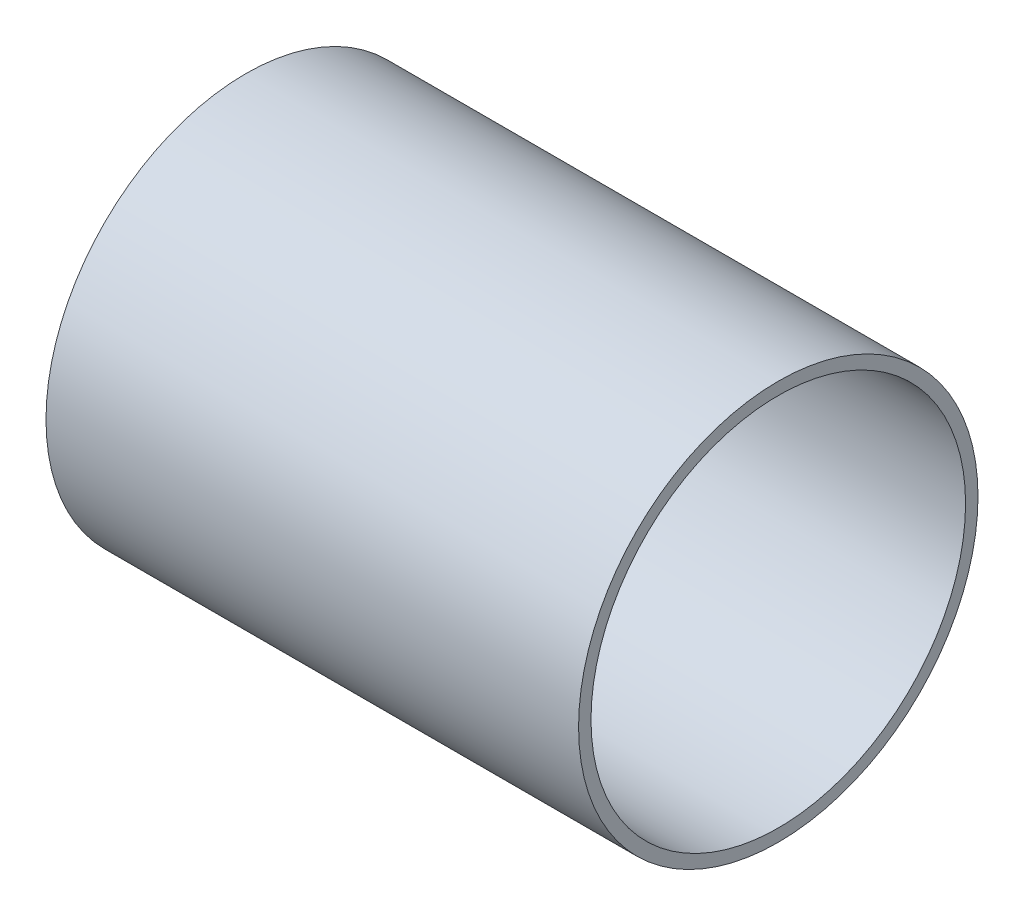
SolidWorks part; units mm, degrees
ref_plane "Front Plane" through (0, 0, 0) normal (0, 0, 1) x (1, 0, 0)
ref_plane "Top Plane" through (0, 0, 0) normal (0, 1, 0) x (1, 0, 0)
ref_plane "Right Plane" through (0, 0, 0) normal (1, 0, 0) x (0, 0, -1)
sketch "Sketch1" plane through (0, 0, 0) normal (1, 0, 0) x (0, 0, -1)
  circle A0 centre (0, 0) radius 14.2875
  circle A1 centre (0, 0) radius 13.3985
  dimension "D1" = 28.575
  dimension "D2" = 26.797
extrude "Boss-Extrude1" add sketch "Sketch1" along normal mid plane 38.1
